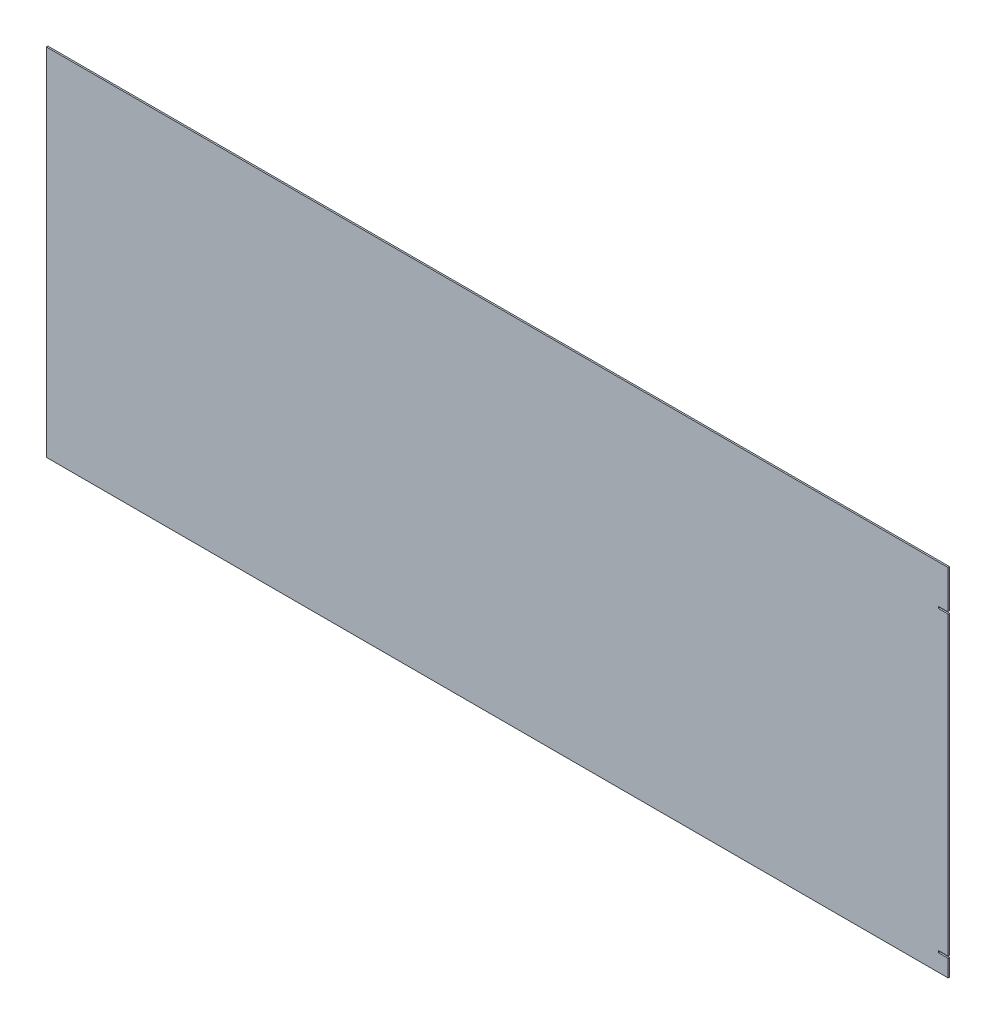
SolidWorks part; units mm, degrees
note: The reader was unsure of these and kept them because the rebuilt part matched: thickness of "Base-Flange1", "Sheet-Metal1", "Sheet-Metal2".
material "AISI 304"
ref_plane "Front Plane" through (0, 0, 0) normal (0, 0, 1) x (1, 0, 0)
ref_plane "Top Plane" through (0, 0, 0) normal (0, 1, 0) x (1, 0, 0)
ref_plane "Right Plane" through (0, 0, 0) normal (1, 0, 0) x (0, 0, -1)
sketch "Sketch1" plane through (0, 0, 0) normal (0, 0, 1) x (1, 0, 0)
  line L1 (600, -236.5) -> (-600, -236.5)
  line L2 (600, -236.5) -> (600, 236.5)
  line L3 (600, 236.5) -> (-600, 236.5)
  line L4 (-600, -236.5) -> (-600, 236.5)
  line L5 (600, -236.5) -> (-600, 236.5) construction
  line L6 (600, 236.5) -> (-600, -236.5) construction
  point P0 (0, 0)
  dimension "D1" = 1200
  dimension "D2" = 473
base flange "Base-Flange1" sketch "Sketch1" thickness 2 reverse thickness direction no parameters "D1"=0.7366
sketch "Sketch2" plane through (600, 0, 0) normal (1, 0, 0) x (0, 0, -1)
  line L0 (0, -236.5) -> (0, 236.5) construction
  line L1 (0, 185.3105) -> (2, 185.3105)
  line L2 (0, 185.3105) -> (0, 182.8105)
  line L3 (0, 182.8105) -> (2, 182.8105)
  line L4 (2, 185.3105) -> (2, 182.8105)
  line L5 (2, -236.5) -> (2, 236.5) construction
  line L7 (0, -211.3207) -> (2, -211.3207)
  line L8 (0, -211.3207) -> (0, -213.8207)
  line L9 (0, -213.8207) -> (2, -213.8207)
  line L10 (2, -211.3207) -> (2, -213.8207)
  dimension "D1" = 2.5
extrude "Cut-Extrude1" cut sketch "Sketch2" against normal blind 13 normal cut yes
fillet "Fillet1" radius 0.74 2 edges at (600, -213.8207, -1) (600, 185.3105, -1)
sketch "Bend-Lines1" [suppressed] plane through (0, 0, 0) normal (0, 1, 0) x (1, 0, 0)
sketch "Bounding-Box1" [suppressed] plane through (0, 0, 0) normal (0, 1, 0) x (1, 0, 0)
sheet metal parameters "Sheet-Metal1" thickness 2 parameters "D1"=0.7366
flat pattern "Flat-Pattern1" [suppressed]
sketch "Bend-Lines2" plane through (0, 0, 0) normal (0, 1, 0) x (1, 0, 0)
sketch3d "Bounding-Box2" [suppressed]
  line L0 (-600, -236.5, 0) -> (600, -236.5, 0) construction
  line L1 (-600, 236.5, 0) -> (600, 236.5, 0) construction
  line L2 (-600, -236.5, 0) -> (-600, 236.5, 0) construction
  line L3 (600, -236.5, 0) -> (600, 236.5, 0) construction
sheet metal parameters "Sheet-Metal2" thickness 2 parameters "D1"=0.7366
flat pattern "Flat-Pattern1"
sketch "Bend-Lines2" plane through (0, 0, 0) normal (0, 1, 0) x (1, 0, 0)
sketch3d "Bounding-Box2" [suppressed]
  line L0 (-600, -236.5, 0) -> (600, -236.5, 0) construction
  line L1 (-600, 236.5, 0) -> (600, 236.5, 0) construction
  line L2 (-600, -236.5, 0) -> (-600, 236.5, 0) construction
  line L3 (600, -236.5, 0) -> (600, 236.5, 0) construction
equation "\"thickness 1\" = 2"
equation "\"thickness radius 1\"= 3.7366"
equation "\"thickness 2\"= 3"
equation "\"connecting flange\"= 35"
equation "\"main length\"= 1200"
equation "\"main width\"= 1200"
equation "\"divider panel distance offset\"= 296"
equation "\"top panel slot length\"= 250"
equation "\"top panel slot width\"= 700"
equation "\"side panel length\"= 1200"
equation "\"side panel width\"= 950"
equation "\"access hatch length\" = \"access hatch cutout length\" + \"access hatch offset\" * 2"
equation "\"access hatch width\" = \"access hatch cutout width\" + \"access hatch offset\" * 2"
equation "\"slotted panel length\" = \"main length\" + 100"
equation "\"slotted panel width\" = \"main width\""
equation "\"slot count x\"= 4"
equation "\"slot count y\"= 9"
equation "\"slot offset\" = \"water tray depth\""
equation "\"slot length\"= 30"
equation "\"slot width\"= 200"
equation "\"slot offset x\" = \"slot length\" + \"slot offset\""
equation "\"slot offset y\" = \"slot width\" + \"slot offset\""
equation "\"drift eliminator size offset\"= 5"
equation "\"drift eliminator depth\" = \"divider panel distance offset\""
equation "\"guide rail flange\"= 40"
equation "\"guid rail flange mount side\"= 20"
equation "\"guid rail back length\" = \"main width\" - \"guide rail flange\" * 2"
equation "\"splash plate length\"= 400"
equation "\"splash plate width\" = \"main width\""
equation "\"splash plate air gap\"= 200"
equation "\"splash plate slot count\"= 11"
equation "\"splash plate slot length\"= 50"
equation "\"splash plate slot height\"= 50"
equation "\"splash plate slot offset\"= 65"
equation "\"water tray depth\"= 150"
equation "\"water tray width\"= 200"
equation "\"dimpled panel length\" = \"main length\" - 200 - \"water tray depth\"/2"
equation "\"dimpled panel top offset\" = \"water tray depth\"/2"
equation "\"dimpled panel width\" = \"main width\""
equation "\"dimple panel slot count\"= 36"
equation "\"dimple panel slot length\"= 8"
equation "\"dimple panel slot width\"= 8"
equation "\"dimple panel slot offset\"= 25"
equation "\"sump base flat section width\"= 300"
equation "\"sump upper depth\"= 300"
equation "\"sump depth\"= 550"
equation "\"leg length\" = \"sump depth\" + 150"
equation "\"leg width\"= 80"
equation "\"leg depth\"= 40"
equation "\"leg support plate size\" = \"leg width\" - \"thickness 2\" * 2"
equation "\"leg base plate thickness\"= 8"
equation "\"D1@Sketch1\"=\"main width\""
equation "\"water tray panel length\"= 473"
equation "\"D2@Sketch1\"=\"water tray panel length\""
equation "\"D7@Sheet-Metal1\"=\"thickness 1\""
equation "\"D1@Sketch2\"=\"thickness 1\" + 0.5"
equation "\"thickness 3\"= 1.2"
equation "\"thichness 4\"= 0.8"
equation "\"connecting flange holes\"= 8"
equation "\"connecting flange hole gap\"= 100"
equation "\"cut out flange\"= 15"
equation "\"access hatch flange\" = 8 "
equation "\"access hatch cutout length\"= 400"
equation "\"access hatch cutout width\"= 600"
equation "\"access hatch cutout offset X\"= 100"
equation "\"access hatch cutout offset Y\"= 100"
equation "\"access hatch offset\"= 90"
equation "\"access hatch hole\"= 9"
equation "\"access hatch hole x gap\"= 350"
equation "\"access hatch hole y gap\"= 200"
equation "\"slot offset bottom\" = 200"
equation "\"drift eliminator cutout width\" = 1140"
equation "\"drift eliminator cutout length\" = 154"
equation "\"drift eliminator access hatch offset\" = 30"
equation "\"drift eliminator access hatch width\" = \"drift eliminator cutout width\" + \"drift eliminator access hatch offset\" * 2"
equation "\"drift eliminator access hatch length\" = \"drift eliminator cutout length\" + \"drift eliminator access hatch offset\" * 2"
equation "\"D1@Cut-Extrude1\"=\"cut out flange\" - \"thickness 1\""
